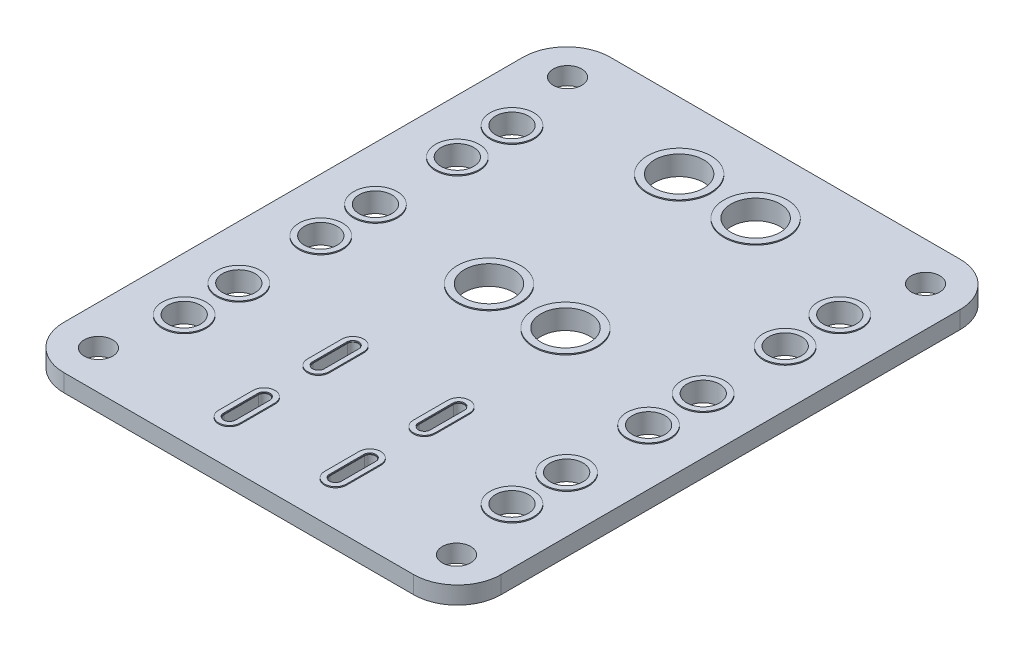
SolidWorks part; units mm, degrees
ref_plane "Alzado" through (0, 0, 0) normal (0, 0, 1) x (1, 0, 0)
ref_plane "Planta" through (0, 0, 0) normal (0, 1, 0) x (1, 0, 0)
ref_plane "Vista lateral" through (0, 0, 0) normal (1, 0, 0) x (0, 0, -1)
sketch "Croquis1" plane through (0, 0, 0) normal (0, 1, 0) x (1, 0, 0)
  line L1 (-16, 25) -> (16, 25)
  line L2 (-20, 21) -> (-20, -21)
  line L3 (-16, -25) -> (16, -25)
  line L4 (20, 21) -> (20, -21)
  line L5 (-20, 25) -> (20, -25) construction
  line L6 (-20, -25) -> (20, 25) construction
  arc A0 (16, 25) -> (20, 21) centre (16, 21) cw
  arc A1 (16, -25) -> (20, -21) centre (16, -21) ccw
  arc A2 (-20, -21) -> (-16, -25) centre (-16, -21) ccw
  arc A3 (-16, 25) -> (-20, 21) centre (-16, 21) ccw
  point P0 (0, 0)
  dimension "D1" = 4
  dimension "D2" = 50
  dimension "D3" = 40
extrude "Saliente-Extruir1" add sketch "Croquis1" along normal mid plane 1.6
sketch "Croquis2" plane through (0, 0.8, 0) normal (0, 1, 0) x (1, 0, 0)
  line L1 (16.383, -21.463) -> (-16.383, -21.463) construction
  line L2 (16.383, -21.463) -> (16.383, 21.463) construction
  line L3 (16.383, 21.463) -> (-16.383, 21.463) construction
  line L4 (-16.383, -21.463) -> (-16.383, 21.463) construction
  line L5 (16.383, -21.463) -> (-16.383, 21.463) construction
  line L6 (16.383, 21.463) -> (-16.383, -21.463) construction
  circle A0 centre (-16.383, 21.463) radius 1.3
  circle A1 centre (16.383, 21.463) radius 1.3
  circle A2 centre (16.383, -21.463) radius 1.3
  circle A3 centre (-16.383, -21.463) radius 1.3
  point P0 (0, 0)
  dimension "D1" = 2.6
  dimension "D2" = 21.463
  dimension "D3" = 16.383
extrude "Cortar-Extruir1" cut sketch "Croquis2" against normal through all both and the other way through all
sketch "Croquis6" plane through (0, 0.8, 0) normal (0, 1, 0) x (1, 0, 0)
  line L0 (-3.5, 18.796) -> (3.5, 18.796) construction
  line L1 (0, 23.1314) -> (0, -25.294) construction
  line L2 (-15, 15) -> (-15, 10) construction
  line L3 (-15, 2.5) -> (-15, -2.5) construction
  line L4 (-15, -10) -> (-15, -15) construction
  line L8 (-3.5, -15.36) -> (3.5, -15.36) construction
  line L9 (-5.7074, 10.0965) -> (6.7794, 10.0965) construction
  line L10 (4.847, -9.721) -> (4.847, -12.871) construction
  line L11 (5.347, -9.721) -> (5.347, -12.871)
  line L12 (4.347, -9.721) -> (4.347, -12.871)
  line L13 (-4.847, -9.721) -> (-4.847, -12.871) construction
  line L14 (-5.347, -9.721) -> (-5.347, -12.871)
  line L15 (-4.347, -9.721) -> (-4.347, -12.871)
  line L16 (4.847, -20.999) -> (4.847, -17.849) construction
  line L17 (5.347, -20.999) -> (5.347, -17.849)
  line L18 (4.347, -20.999) -> (4.347, -17.849)
  line L19 (-4.847, -20.999) -> (-4.847, -17.849) construction
  line L20 (-5.347, -20.999) -> (-5.347, -17.849)
  line L21 (-4.347, -20.999) -> (-4.347, -17.849)
  line L22 (-3.5, 1.397) -> (3.5, 1.397) construction
  line L23 (4.847, -11.296) -> (4.847, -19.424) construction
  circle A0 centre (-3.5, 18.796) radius 2.25
  circle A1 centre (3.5, 18.796) radius 2.25
  circle A2 centre (-15, 2.5) radius 1.5
  circle A3 centre (-15, -2.5) radius 1.5
  circle A4 centre (-15, 10) radius 1.5
  circle A5 centre (-15, 15) radius 1.5
  circle A6 centre (-15, -10) radius 1.5
  circle A7 centre (-15, -15) radius 1.5
  circle A8 centre (15, -15) radius 1.5
  circle A9 centre (15, -10) radius 1.5
  circle A10 centre (15, 15) radius 1.5
  circle A11 centre (15, 10) radius 1.5
  circle A12 centre (15, -2.5) radius 1.5
  circle A13 centre (15, 2.5) radius 1.5
  arc A16 (5.347, -9.721) -> (4.347, -9.721) centre (4.847, -9.721) ccw
  arc A17 (4.347, -12.871) -> (5.347, -12.871) centre (4.847, -12.871) ccw
  arc A18 (-5.347, -9.721) -> (-4.347, -9.721) centre (-4.847, -9.721) cw
  arc A19 (-4.347, -12.871) -> (-5.347, -12.871) centre (-4.847, -12.871) cw
  arc A20 (5.347, -20.999) -> (4.347, -20.999) centre (4.847, -20.999) cw
  arc A21 (4.347, -17.849) -> (5.347, -17.849) centre (4.847, -17.849) cw
  arc A22 (-5.347, -20.999) -> (-4.347, -20.999) centre (-4.847, -20.999) ccw
  arc A23 (-4.347, -17.849) -> (-5.347, -17.849) centre (-4.847, -17.849) ccw
  circle A24 centre (3.5, 1.397) radius 2.25
  circle A25 centre (-3.5, 1.397) radius 2.25
  point P4 (0, 18.796)
  point P32 (-15, 0)
  point P33 (-15, 12.5)
  point P34 (-15, -12.5)
  point P46 (4.847, -11.296)
  point P54 (-4.847, -11.296)
  point P61 (4.847, -19.424)
  point P68 (-4.847, -19.424)
  point P73 (4.847, -15.36)
  point P74 (6.347, -12.4664)
  point P75 (6.347, -12.1592)
  dimension "D1" = 3
  dimension "D8" = 4.5
  dimension "D2" = 5
  dimension "D3" = 5
  dimension "D4" = 5
  dimension "D5" = 15
  dimension "D6" = 12.5
  dimension "D7" = 12.5
  dimension "D9" = 7
  dimension "D10" = 18.796
  dimension "D11" = 1
  dimension "D12" = 3.15
  dimension "D13" = 1.397
  dimension "D14" = 4.847
  dimension "D15" = 15.36
  dimension "D16" = 8.128
extrude "Cortar-Extruir3" cut sketch "Croquis6" against normal through all
sketch "Croquis7" plane through (0, 0, 0) normal (0, 1, 0) x (1, 0, 0)
  line L0 (0, 6.6749) -> (0, -3.6027) construction
  line L8 (-4.297, -12.871) -> (-4.297, -9.721)
  line L9 (-5.397, -9.721) -> (-5.397, -12.871)
  line L10 (-4.297, -12.871) -> (-4.297, -9.721)
  line L11 (-5.397, -9.721) -> (-5.397, -12.871)
  line L13 (5.397, -12.871) -> (5.397, -9.721)
  line L14 (4.297, -9.721) -> (4.297, -12.871)
  line L15 (5.397, -12.871) -> (5.397, -9.721)
  line L16 (4.297, -9.721) -> (4.297, -12.871)
  line L22 (-4.297, -20.999) -> (-4.297, -17.849)
  line L23 (-5.397, -17.849) -> (-5.397, -20.999)
  line L24 (-4.297, -20.999) -> (-4.297, -17.849)
  line L25 (-5.397, -17.849) -> (-5.397, -20.999)
  line L31 (5.397, -20.999) -> (5.397, -17.849)
  line L32 (4.297, -17.849) -> (4.297, -20.999)
  line L33 (5.397, -20.999) -> (5.397, -17.849)
  line L34 (-3.847, -12.871) -> (-3.847, -9.721)
  line L35 (-5.847, -9.721) -> (-5.847, -12.871)
  line L36 (-3.847, -12.871) -> (-3.847, -9.721)
  line L37 (-5.847, -9.721) -> (-5.847, -12.871)
  line L38 (4.297, -17.849) -> (4.297, -20.999)
  line L44 (5.847, -12.871) -> (5.847, -9.721)
  line L45 (3.847, -9.721) -> (3.847, -12.871)
  line L46 (5.847, -12.871) -> (5.847, -9.721)
  line L47 (3.847, -9.721) -> (3.847, -12.871)
  line L54 (-5.847, -17.849) -> (-5.847, -20.999)
  line L55 (-3.847, -20.999) -> (-3.847, -17.849)
  line L56 (-5.847, -17.849) -> (-5.847, -20.999)
  line L57 (-3.847, -20.999) -> (-3.847, -17.849)
  line L64 (5.847, -20.999) -> (5.847, -17.849)
  line L65 (3.847, -17.849) -> (3.847, -20.999)
  line L66 (5.847, -20.999) -> (5.847, -17.849)
  line L67 (3.847, -17.849) -> (3.847, -20.999)
  circle A0 centre (-15, -15) radius 1.5
  circle A1 centre (-15, -10) radius 1.5
  circle A2 centre (-15, -2.5) radius 1.5
  circle A3 centre (-15, 2.5) radius 1.5
  circle A4 centre (-15, 10) radius 1.5
  circle A5 centre (-15, 15) radius 1.5
  circle A6 centre (-15, 15) radius 1.5 construction
  circle A7 centre (-15, 15) radius 2
  circle A8 centre (-15, 10) radius 2
  circle A9 centre (-15, 2.5) radius 2
  circle A10 centre (-15, -2.5) radius 2
  circle A11 centre (-15, -15) radius 2
  circle A12 centre (-15, -10) radius 2
  circle A13 centre (-3.5, 18.796) radius 2.25
  circle A14 centre (-3.5, 18.796) radius 2.8949
  circle A15 centre (3.5, 18.796) radius 2.8949
  circle A16 centre (3.5, 18.796) radius 2.25
  circle A17 centre (15, -10) radius 2
  circle A18 centre (15, -15) radius 2
  circle A19 centre (15, -2.5) radius 2
  circle A20 centre (15, 2.5) radius 2
  circle A21 centre (15, 10) radius 2
  circle A22 centre (15, 15) radius 2
  circle A23 centre (15, 15) radius 1.5
  circle A24 centre (15, 10) radius 1.5
  circle A25 centre (15, 2.5) radius 1.5
  circle A26 centre (15, -2.5) radius 1.5
  circle A27 centre (15, -10) radius 1.5
  circle A28 centre (15, -15) radius 1.5
  circle A29 centre (3.5, 1.397) radius 2.25
  circle A30 centre (3.5, 1.397) radius 2.8949
  circle A31 centre (-3.5, 1.397) radius 2.8949
  circle A32 centre (-3.5, 1.397) radius 2.25
  arc A39 (-5.397, -12.871) -> (-4.297, -12.871) centre (-4.847, -12.871) ccw
  arc A40 (-4.297, -9.721) -> (-5.397, -9.721) centre (-4.847, -9.721) ccw
  arc A41 (-5.397, -12.871) -> (-4.297, -12.871) centre (-4.847, -12.871) ccw
  arc A42 (-4.297, -9.721) -> (-5.397, -9.721) centre (-4.847, -9.721) ccw
  arc A43 (4.297, -12.871) -> (5.397, -12.871) centre (4.847, -12.871) ccw
  arc A44 (5.397, -9.721) -> (4.297, -9.721) centre (4.847, -9.721) ccw
  arc A45 (4.297, -12.871) -> (5.397, -12.871) centre (4.847, -12.871) ccw
  arc A46 (5.397, -9.721) -> (4.297, -9.721) centre (4.847, -9.721) ccw
  arc A52 (-5.397, -20.999) -> (-4.297, -20.999) centre (-4.847, -20.999) ccw
  arc A53 (-4.297, -17.849) -> (-5.397, -17.849) centre (-4.847, -17.849) ccw
  arc A54 (-5.397, -20.999) -> (-4.297, -20.999) centre (-4.847, -20.999) ccw
  arc A55 (-4.297, -17.849) -> (-5.397, -17.849) centre (-4.847, -17.849) ccw
  arc A61 (4.297, -20.999) -> (5.397, -20.999) centre (4.847, -20.999) ccw
  arc A62 (5.397, -17.849) -> (4.297, -17.849) centre (4.847, -17.849) ccw
  arc A63 (4.297, -20.999) -> (5.397, -20.999) centre (4.847, -20.999) ccw
  arc A64 (5.397, -17.849) -> (4.297, -17.849) centre (4.847, -17.849) ccw
  arc A67 (-5.847, -12.871) -> (-3.847, -12.871) centre (-4.847, -12.871) ccw
  arc A68 (-3.847, -9.721) -> (-5.847, -9.721) centre (-4.847, -9.721) ccw
  arc A69 (-5.847, -12.871) -> (-3.847, -12.871) centre (-4.847, -12.871) ccw
  arc A70 (-3.847, -9.721) -> (-5.847, -9.721) centre (-4.847, -9.721) ccw
  arc A75 (3.847, -12.871) -> (5.847, -12.871) centre (4.847, -12.871) ccw
  arc A76 (5.847, -9.721) -> (3.847, -9.721) centre (4.847, -9.721) ccw
  arc A77 (3.847, -12.871) -> (5.847, -12.871) centre (4.847, -12.871) ccw
  arc A78 (5.847, -9.721) -> (3.847, -9.721) centre (4.847, -9.721) ccw
  arc A83 (-5.847, -20.999) -> (-3.847, -20.999) centre (-4.847, -20.999) ccw
  arc A84 (-3.847, -17.849) -> (-5.847, -17.849) centre (-4.847, -17.849) ccw
  arc A85 (-5.847, -20.999) -> (-3.847, -20.999) centre (-4.847, -20.999) ccw
  arc A86 (-3.847, -17.849) -> (-5.847, -17.849) centre (-4.847, -17.849) ccw
  arc A91 (5.847, -17.849) -> (3.847, -17.849) centre (4.847, -17.849) ccw
  arc A92 (3.847, -20.999) -> (5.847, -20.999) centre (4.847, -20.999) ccw
  arc A93 (5.847, -17.849) -> (3.847, -17.849) centre (4.847, -17.849) ccw
  arc A94 (3.847, -20.999) -> (5.847, -20.999) centre (4.847, -20.999) ccw
  point P54 (-3.5, 1.397)
  point P55 (3.5, 1.397)
  point P62 (-3.5, -18.796)
  dimension "D1" = 4
  dimension "D2" = 0.5
  dimension "D3" = 0.5
  dimension "D4" = 0.5
  dimension "D5" = 0.5
  dimension "D6" = 0.05
  dimension "D7" = 0.05
  dimension "D8" = 0.05
  dimension "D9" = 0.05
extrude "Saliente-Extruir3" add sketch "Croquis7" along normal mid plane 1.8
